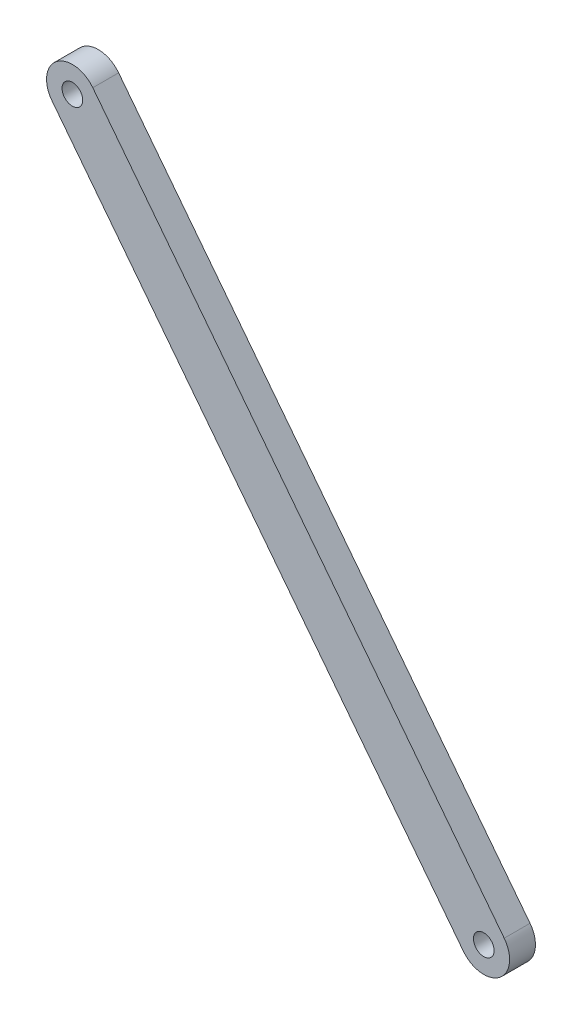
SolidWorks part; units mm, degrees
ref_plane "Front Plane" through (0, 0, 0) normal (0, 0, 1) x (1, 0, 0)
ref_plane "Top Plane" through (0, 0, 0) normal (0, 1, 0) x (1, 0, 0)
ref_plane "Right Plane" through (0, 0, 0) normal (1, 0, 0) x (0, 0, -1)
sketch "Sketch1" plane through (0, 0, 0) normal (0, 0, 1) x (1, 0, 0)
  line L2 (-97.6599, 152.356) -> (-18.0229, 49.6041) construction
  line L3 (-25.9269, 43.4782) -> (-105.5639, 146.2301) construction
  line L4 (-97.6599, 152.356) -> (-18.0229, 49.6041)
  line L5 (-25.9269, 43.4782) -> (-105.5639, 146.2301)
  circle A6 centre (-101.6119, 149.293) radius 2 construction
  circle A7 centre (-21.9749, 46.5411) radius 2 construction
  arc A8 (-25.9269, 43.4782) -> (-18.0229, 49.6041) centre (-21.9749, 46.5411) ccw construction
  arc A9 (-97.6599, 152.356) -> (-105.5639, 146.2301) centre (-101.6119, 149.293) ccw construction
  circle A10 centre (-101.6119, 149.293) radius 2
  circle A11 centre (-21.9749, 46.5411) radius 2
  arc A12 (-25.9269, 43.4782) -> (-18.0229, 49.6041) centre (-21.9749, 46.5411) ccw
  arc A13 (-97.6599, 152.356) -> (-105.5639, 146.2301) centre (-101.6119, 149.293) ccw
extrude "Boss-Extrude1" add sketch "Sketch1" along normal blind 5 from offset 5
